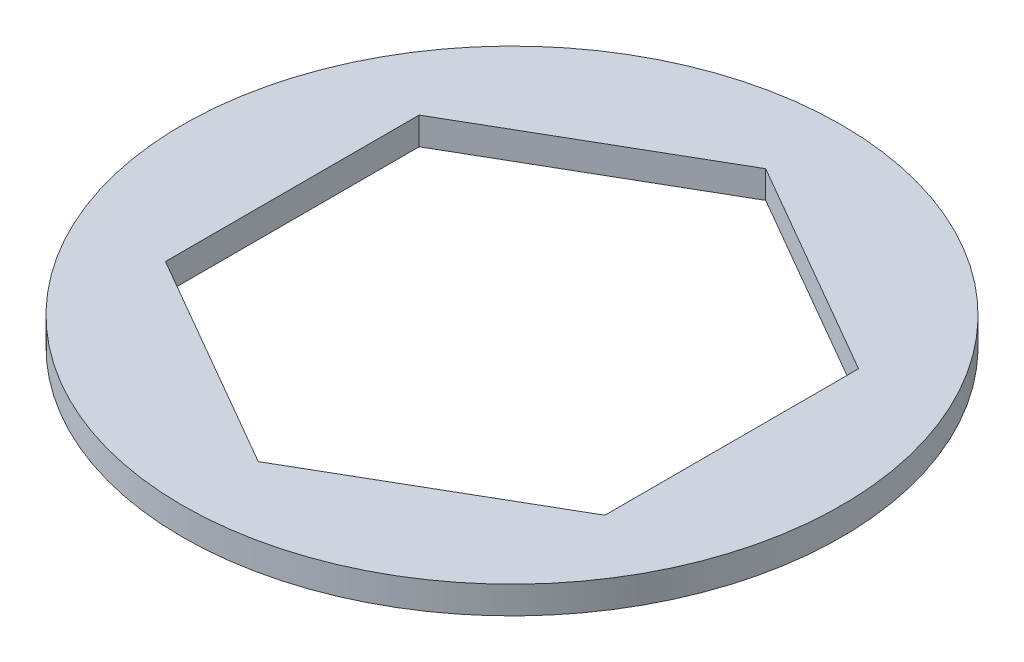
SolidWorks part; units mm, degrees
material "PET"
ref_plane "Front Plane" through (0, 0, 0) normal (0, 0, 1) x (1, 0, 0)
ref_plane "Top Plane" through (0, 0, 0) normal (0, 1, 0) x (1, 0, 0)
ref_plane "Right Plane" through (0, 0, 0) normal (1, 0, 0) x (0, 0, -1)
sketch "Sketch1" plane through (0, 0, 0) normal (0, 1, 0) x (1, 0, 0)
  line L1 (6.35, 3.6662) -> (0, 7.3323)
  line L2 (0, 7.3323) -> (-6.35, 3.6662)
  line L3 (-6.35, 3.6662) -> (-6.35, -3.6662)
  line L4 (-6.35, -3.6662) -> (0, -7.3323)
  line L5 (0, -7.3323) -> (6.35, -3.6662)
  line L6 (6.35, -3.6662) -> (6.35, 3.6662)
  circle A0 centre (0, 0) radius 9.525
  circle A2 centre (0, 0) radius 6.35 construction
  dimension "D1" = 12.7
  dimension "D2" = 19.05
extrude "Boss-Extrude1" add sketch "Sketch1" along normal blind 0.7937
